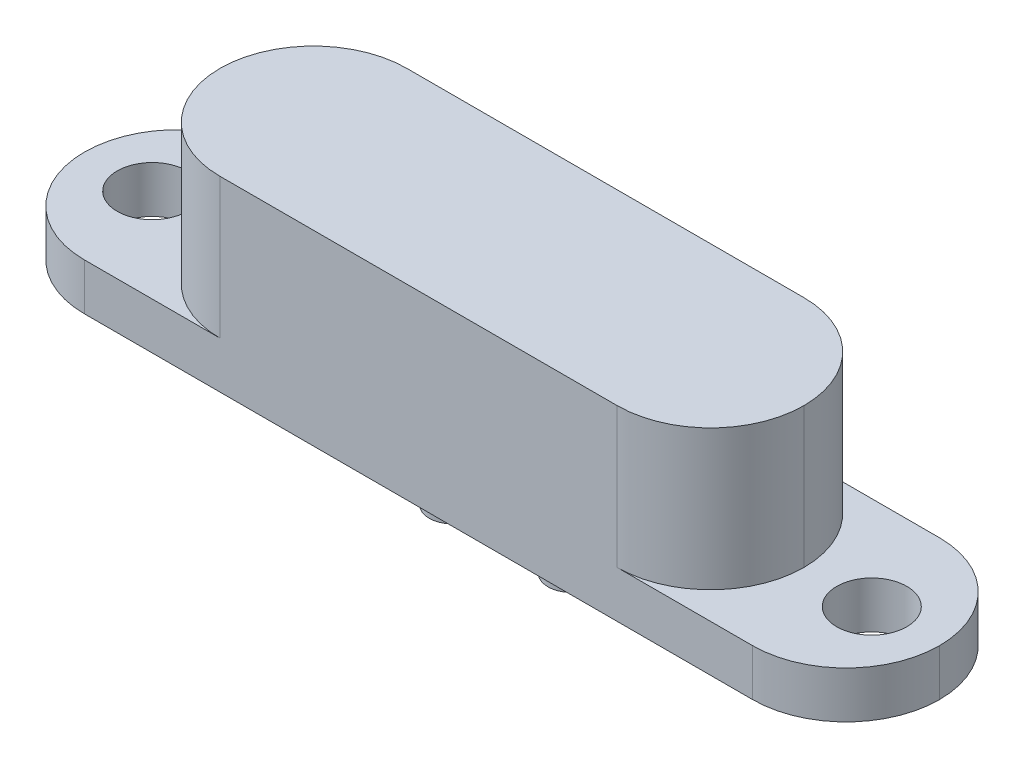
SolidWorks part; units mm, degrees
ref_plane "前视基准面" through (0, 0, 0) normal (0, 0, 1) x (1, 0, 0)
ref_plane "上视基准面" through (0, 0, 0) normal (0, 1, 0) x (1, 0, 0)
ref_plane "右视基准面" through (0, 0, 0) normal (1, 0, 0) x (0, 0, -1)
other "Configuration Table"
sketch "草图1" plane through (0, 0, 0) normal (0, 1, 0) x (1, 0, 0)
  line L1 (-9.15, -2) -> (9.15, -2)
  line L2 (-9.15, -2) -> (-9.15, 2)
  line L3 (-9.15, 2) -> (9.15, 2)
  line L4 (9.15, -2) -> (9.15, 2)
  line L5 (-9.15, -2) -> (9.15, 2) construction
  line L6 (-9.15, 2) -> (9.15, -2) construction
  line L7 (-6.25, -2) -> (6.25, -2)
  line L8 (-6.25, -2) -> (-6.25, 2)
  line L9 (-6.25, 2) -> (6.25, 2)
  line L10 (6.25, -2) -> (6.25, 2)
  line L11 (-6.25, -2) -> (6.25, 2) construction
  line L12 (-6.25, 2) -> (6.25, -2) construction
  point P0 (0, 0)
  point P7 (0, 0)
  dimension "D1" = 4
  dimension "D2" = 18.3
  dimension "D3" = 12.5
extrude "凸台-拉伸1" add sketch "草图1" along normal blind 4 contours L8 L9 L10 L7
fillet "圆角1" radius 2 4 edges at (6.25, 2, -2) (6.25, 2, 2) (-6.25, 2, 2) (-6.25, 2, -2)
extrude "凸台-拉伸2" add sketch "草图1<3>" along normal blind 1 contours L2 L3 L4 L1
sketch "草图1<3>" plane through (0, 0, 0) normal (0, 1, 0) x (1, 0, 0) same geometry as "草图1"
fillet "圆角2" radius 2 4 edges at (9.15, 0.5, 2) (9.15, 0.5, -2) (-9.15, 0.5, 2) (-9.15, 0.5, -2)
sketch "草图2" plane through (0, 1, 0) normal (0, 1, 0) x (1, 0, 0)
  line L0 (-9.15, 0) -> (-6.25, 0) construction
  line L1 (6.25, 0) -> (9.15, 0) construction
  arc A0 (-6.25, 0) -> (-4.25, -2) centre (-4.25, 0) ccw construction
  circle A1 centre (-7.7, 0) radius 0.75
  arc A2 (4.25, -2) -> (6.25, 0) centre (4.25, 0) ccw construction
  circle A3 centre (7.7, 0) radius 0.75
  dimension "D1" = 1.5
extrude "切除-拉伸1" cut sketch "草图2" against normal through all
sketch "草图3" plane through (0, 0, 0) normal (0, -1, 0) x (1, 0, 0)
  line L0 (-1.27, 0) -> (0, 0) construction
  line L7 (0, 0) -> (1.27, 0) construction
  circle A0 centre (-1.27, 0) radius 0.5
  circle A1 centre (1.27, 0) radius 0.5
  point P0 (0, 0)
  point P1 (0, 0)
  dimension "D2" = 1
  dimension "D1" = 2.54
extrude "凸台-拉伸3" add sketch "草图3" along normal blind 5.6 from surface starting at face at (0, 4, 0)
